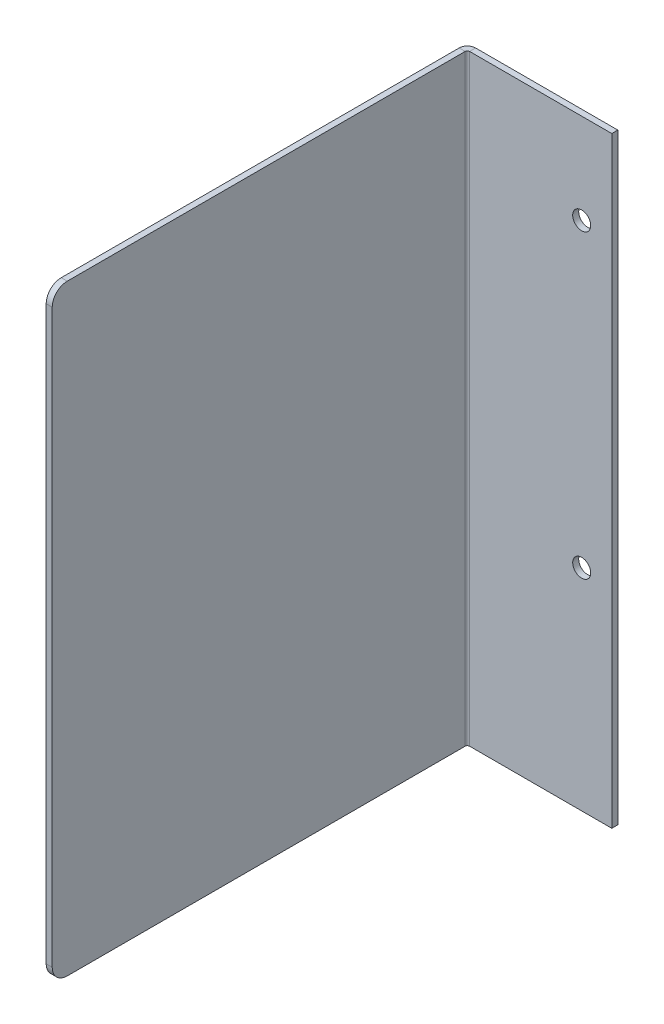
SolidWorks part; units mm, degrees
note: The reader was unsure of these and kept them because the rebuilt part matched: flange length of "边线-法兰1".
ref_plane "前视基准面" through (0, 0, 0) normal (0, 0, 1) x (1, 0, 0)
ref_plane "上视基准面" through (0, 0, 0) normal (0, 1, 0) x (1, 0, 0)
ref_plane "右视基准面" through (0, 0, 0) normal (1, 0, 0) x (0, 0, -1)
sketch "草图1" plane through (0, 0, 0) normal (0, 0, 1) x (1, 0, 0)
  line L1 (-8.3376, 7.7494) -> (41.6624, 7.7494)
  line L2 (-8.3376, 7.7494) -> (-8.3376, -192.2506)
  line L3 (-8.3376, -192.2506) -> (41.6624, -192.2506)
  line L4 (41.6624, 7.7494) -> (41.6624, -192.2506)
  dimension "D1" = 50
  dimension "D2" = 200
sheet metal parameters "钣金1" thickness 2 parameters "D1"=0.7366
base flange "基体-法兰1" sketch "草图1" thickness 2 reverse thickness direction no parameters "D1"=0.7366
ref_plane "基准面4" through (-8.3376, 7.7494, 0) normal (0, -1, 0) x (-1, 0, 0)
edge flange "边线-法兰1" sketch "草图7" flange angle 90 flange length 140 flange position material inside bend radius 0.7366 thickness 2 relief rectangular parameters "D6"=10
sketch "草图7" plane through (-8.3376, 0, 0) normal (-1, 0, 0) x (0, -1, 0)
  line L2 (-7.7494, 0) -> (-7.7494, 138)
  line L3 (-7.7494, 138) -> (192.2506, 138)
  line L4 (192.2506, 138) -> (192.2506, 0)
  line L7 (-7.7494, 0) -> (192.2506, 0) construction
  line L8 (-7.7494, 0) -> (192.2506, 0)
bend "边线折弯1" bend radius 0.7366 bend angle 90 parameters "D5"=1
sketch "草图8" plane through (0, 0, 0) normal (0, 0, 1) x (1, 0, 0)
  line L0 (41.6624, 7.7494) -> (-5.601, 7.7494) construction
  line L1 (41.6624, -192.2506) -> (41.6624, 7.7494) construction
  circle A0 centre (31.6624, -22.2506) radius 3
  dimension "D1" = 30
  dimension "D2" = 10
extrude "切除-拉伸1" cut sketch "草图8" against normal blind 10 normal cut yes
pattern_linear "阵列(线性)1" count 2 spacing 100 along (0, -1, 0) of "切除-拉伸1"
fillet "圆角2" radius 5 1 edges at (-7.3376, 7.7494, 138)
fillet "圆角3" radius 5 1 edges at (-7.3376, -192.2506, 138)
flat pattern "平板型式1" [suppressed]
sketch "折弯-线1" plane through (0, 0, 0) normal (0, 0, 1) x (1, 0, 0)
  line L0 (-6.9649, 7.7494) -> (-6.9649, -192.2506) construction
  line L1 (-6.9649, 7.7494) -> (-6.9649, -192.2506) construction
sketch3d "边界框1" [suppressed]
  line L0 (41.6624, -192.2506, 0) -> (41.6624, 7.7494, 0) construction
  line L1 (-145.5922, -192.2506, 0) -> (-145.5922, 7.7494, 0) construction
  line L2 (41.6624, -192.2506, 0) -> (-145.5922, -192.2506, 0) construction
  line L3 (41.6624, 7.7494, 0) -> (-145.5922, 7.7494, 0) construction
bend of the flat pattern "展平-<边线折弯1>1"
